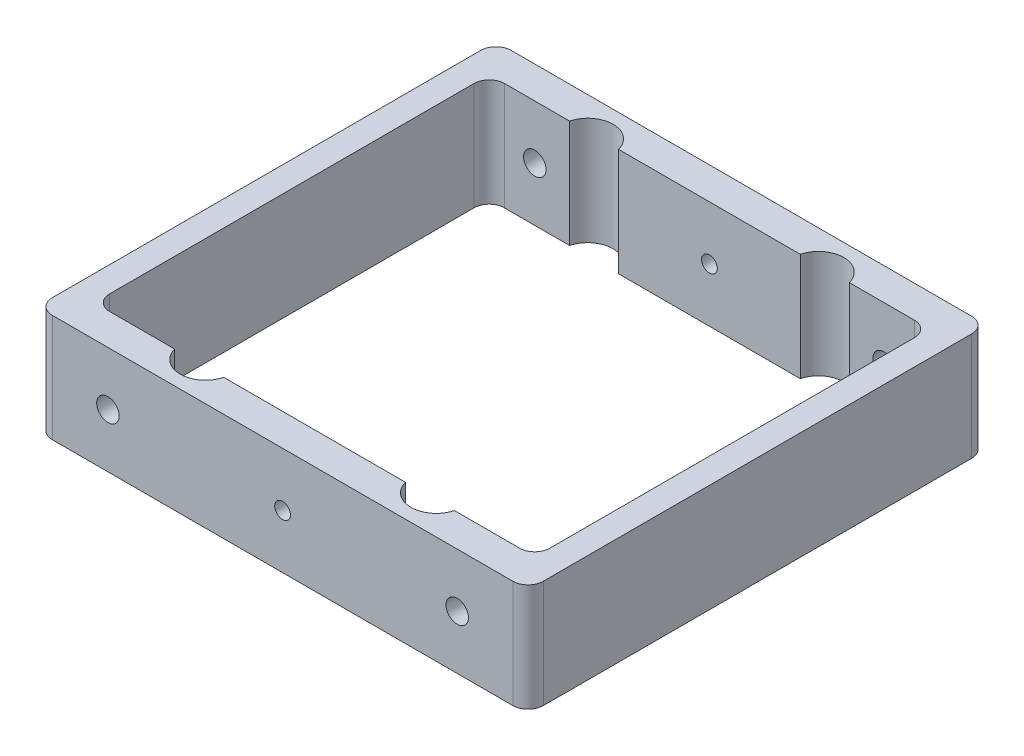
SolidWorks part; units mm, degrees
ref_plane "Front Plane" through (0, 0, 0) normal (0, 0, 1) x (1, 0, 0)
ref_plane "Top Plane" through (0, 0, 0) normal (0, 1, 0) x (1, 0, 0)
ref_plane "Right Plane" through (0, 0, 0) normal (1, 0, 0) x (0, 0, -1)
sketch "Sketch1" plane through (0, 0, 0) normal (0, 1, 0) x (1, 0, 0)
  line L1 (0, 0) -> (60, 0)
  line L2 (0, 0) -> (0, -6.32)
  line L3 (0, -6.32) -> (60, -6.32)
  line L4 (60, 0) -> (60, -6.32)
  point P7 (0, 0)
  dimension "D1" = 60
  dimension "D2" = 6.32
extrude "Boss-Extrude1" add sketch "Sketch1" along normal mid plane 21.28
sketch "Sketch2" plane through (0, 10.64, 0) normal (0, 1, 0) x (1, 0, 0)
  line L0 (0, 0) -> (0, -6.32) construction
  line L1 (0, -6.32) -> (60, -6.32) construction
  line L2 (60, -6.32) -> (60, 0) construction
  circle A0 centre (7.21, 1.25) radius 5
  circle A1 centre (52.79, 1.25) radius 5
  dimension "D1" = 7.21
  dimension "D3" = 7.21
  dimension "D2" = 7.57
  dimension "D4" = 7.57
extrude "Cut-Extrude1" cut sketch "Sketch2" against normal through all
sketch "Sketch3" plane through (60, 0, 0) normal (1, 0, 0) x (0, 0, -1)
  line L1 (-6.32, 10.64) -> (0, 10.64)
  line L2 (-6.32, 10.64) -> (-6.32, -10.64)
  line L3 (-6.32, -10.64) -> (0, -10.64)
  line L4 (0, 10.64) -> (0, -10.64)
extrude "Boss-Extrude2" add sketch "Sketch3" along normal blind 18.5
sketch "Sketch4" plane through (0, 0, 0) normal (-1, 0, 0) x (0, 0, 1)
  line L1 (0, 10.64) -> (6.32, 10.64)
  line L2 (0, 10.64) -> (0, -10.64)
  line L3 (0, -10.64) -> (6.32, -10.64)
  line L4 (6.32, 10.64) -> (6.32, -10.64)
extrude "Boss-Extrude3" add sketch "Sketch4" along normal blind 18.5
sketch "Sketch5" plane through (0, 0, 0) normal (0, 0, -1) x (-1, 0, 0)
  line L5 (-2.3688, -10.64) -> (18.5, -10.64) construction
  line L6 (18.5, 10.64) -> (13.5, 10.64)
  line L7 (18.5, 10.64) -> (18.5, -10.64)
  line L8 (18.5, -10.64) -> (13.5, -10.64)
  line L9 (13.5, 10.64) -> (13.5, -10.64)
  dimension "D1" = 5
extrude "Boss-Extrude6" add sketch "Sketch5" along normal blind 84.33
sketch "Sketch6" plane through (0, 0, 0) normal (0, 0, -1) x (-1, 0, 0)
  line L1 (-78.5, 10.64) -> (-73.5, 10.64)
  line L2 (-78.5, 10.64) -> (-78.5, -10.652)
  line L3 (-78.5, -10.652) -> (-73.5, -10.652)
  line L4 (-73.5, 10.64) -> (-73.5, -10.652)
  dimension "D1" = 5
extrude "Boss-Extrude7" add sketch "Sketch6" along normal blind 84.33
sketch "Sketch7" plane through (73.5, 0, 0) normal (-1, 0, 0) x (0, 0, 1)
  line L0 (-84.33, -10.652) -> (0, -10.652) construction
  line L1 (-84.33, 10.64) -> (-78.01, 10.64)
  line L2 (-84.33, 10.64) -> (-84.33, -10.652)
  line L3 (-84.33, -10.652) -> (-78.01, -10.652)
  line L4 (-78.01, 10.64) -> (-78.01, -10.652)
  dimension "D1" = 6.32
extrude "Boss-Extrude8" add sketch "Sketch7" along normal through all
sketch "Sketch9" plane through (0, 10.64, 0) normal (0, 1, 0) x (1, 0, 0)
  line L0 (-18.5, 84.33) -> (78.5, 84.33) construction
  circle A0 centre (7.21, 76.76) radius 5
  circle A1 centre (52.79, 76.76) radius 5
  dimension "D1" = 7.57
  dimension "D2" = 7.57
  dimension "D3" = 10
extrude "Cut-Extrude2" cut sketch "Sketch9" against normal through all
sketch "Sketch10" plane through (0, 0, -84.33) normal (0, 0, -1) x (-1, 0, 0)
  line L0 (-78.5, 10.64) -> (-78.5, -10.652) construction
  line L1 (-78.5, -10.64) -> (18.5, -10.64) construction
  line L2 (-30, -10.64) -> (-30, 10.64) construction
  line L3 (18.5, 10.64) -> (-78.5, 10.64) construction
  circle A0 centre (-64.5, 0.005) radius 2.22
  circle A1 centre (4.5, 0.005) radius 2.22
  point P12 (0, 0)
  dimension "D1" = 14
  dimension "D2" = 10.645
extrude "Cut-Extrude3" cut sketch "Sketch10" against normal through all
fillet "Fillet1" radius 3 8 edges at (-18.5, 0, 6.32) (78.5, 0, 6.32) (78.5, -0.006, -84.33) (-18.5, -0.006, -84.33) (-13.5, 0, -78.01) (-13.5, 0, 0) (73.5, -0.006, -78.01) (73.5, 0, 0)
sketch "Sketch13" plane through (0, 0, -84.33) normal (0, 0, -1) x (-1, 0, 0)
  line L1 (-75.5, 10.64) -> (-75.5, -10.652) construction
  line L2 (-75.5, -10.64) -> (15.5, -10.64) construction
  circle A0 centre (-30, 0.005) radius 1.555
  dimension "D1" = 45.5
  dimension "D2" = 10.645
extrude "Cut-Extrude4" cut sketch "Sketch13" against normal through all
